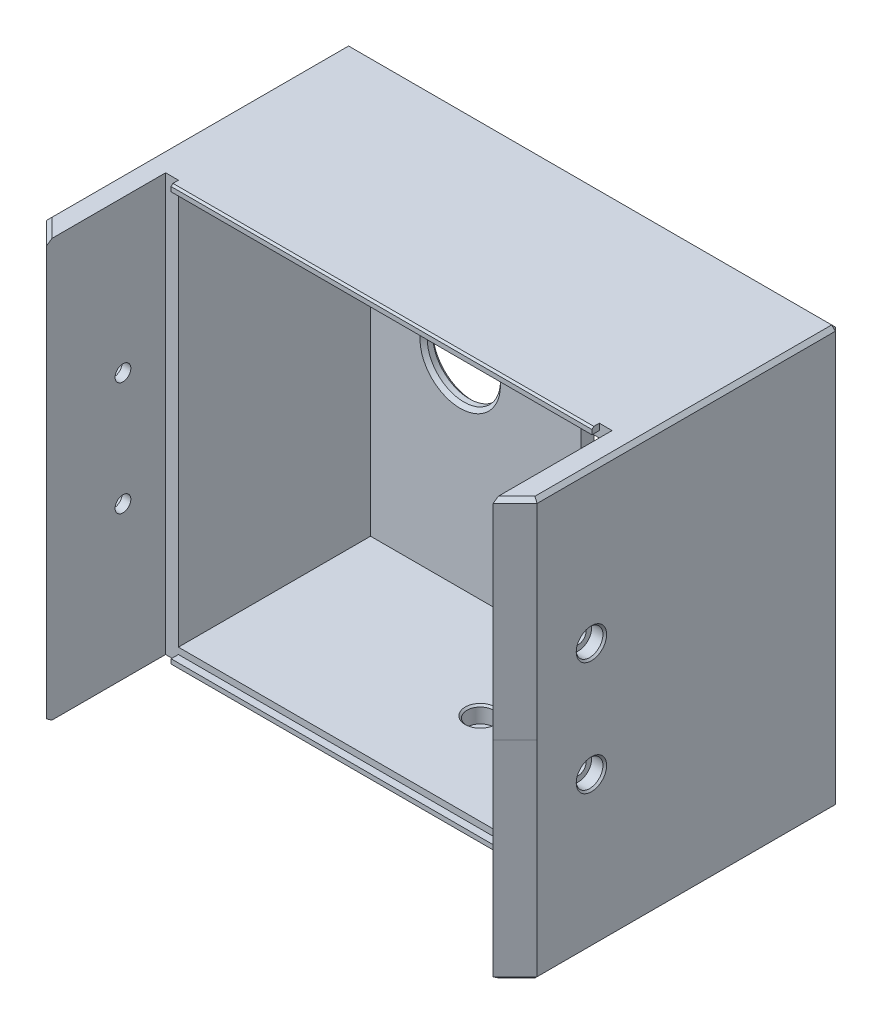
SolidWorks part; units mm, degrees
ref_plane "Front Plane" through (0, 0, 0) normal (0, 0, 1) x (1, 0, 0)
ref_plane "Top Plane" through (0, 0, 0) normal (0, 1, 0) x (1, 0, 0)
ref_plane "Right Plane" through (0, 0, 0) normal (1, 0, 0) x (0, 0, -1)
sketch "Sketch1" plane through (0, 0, 0) normal (0, 0, 1) x (1, 0, 0)
  line L1 (0, 0) -> (134, 0)
  line L2 (0, 0) -> (0, 57)
  line L3 (0, 57) -> (134, 57)
  line L4 (134, 0) -> (134, 57)
  dimension "D1" = 134
  dimension "D2" = 57
extrude "Boss-Extrude1" add sketch "Sketch1" along normal blind 250
sketch "Sketch2" plane through (0, 0, 250) normal (0, 0, 1) x (1, 0, 0)
  line L0 (0, 57) -> (0, 0) construction
  line L1 (9.5, 53.5) -> (124.5, 53.5)
  line L2 (9.5, 53.5) -> (9.5, 0)
  line L3 (9.5, 0) -> (124.5, 0)
  line L4 (124.5, 53.5) -> (124.5, 0)
  line L5 (134, 57) -> (0, 57) construction
  line L6 (134, 0) -> (134, 57) construction
  line L8 (0, 0) -> (134, 0) construction
  dimension "D1" = 9.5
  dimension "D2" = 3.5
  dimension "D3" = 9.5
extrude "Cut-Extrude1" cut sketch "Sketch2" against normal blind 246.5
sketch "Sketch3" plane through (0, 57, 0) normal (0, 1, 0) x (1, 0, 0)
  line L0 (134, -250) -> (0, -250) construction
  line L1 (9.5, -250) -> (124.5, -250)
  line L2 (9.5, -250) -> (9.5, -56)
  line L3 (9.5, -56) -> (124.5, -56)
  line L4 (124.5, -250) -> (124.5, -56)
  line L5 (0, -250) -> (0, 0) construction
  line L6 (134, -250) -> (134, 0) construction
  dimension "D1" = 9.5
  dimension "D2" = 9.5
  dimension "D3" = 194
extrude "Cut-Extrude2" cut sketch "Sketch3" against normal up to surface (3.5 mm away) up to face at (67, 53.5, 126.75)
sketch "Sketch4" plane through (0, 0, 0) normal (0, -1, 0) x (1, 0, 0)
  line L0 (67, 250) -> (67, 0) construction
  line L1 (0, 250) -> (9.5, 250) construction
  line L2 (9.5, 0) -> (124.5, 0) construction
  line L3 (0, 250) -> (0, 0) construction
  line L4 (0, 202.5) -> (6, 202.5)
  line L5 (0, 202.5) -> (0, 82.5)
  line L6 (0, 82.5) -> (6, 82.5)
  line L7 (6, 202.5) -> (6, 82.5)
  line L8 (128, 202.5) -> (128, 82.5)
  line L9 (134, 82.5) -> (128, 82.5)
  line L10 (134, 202.5) -> (134, 82.5)
  line L11 (134, 202.5) -> (128, 202.5)
  line L13 (0, 250) -> (9.5, 250) construction
  dimension "D1" = 47.5
  dimension "D2" = 6
  dimension "D3" = 120
extrude "Cut-Extrude3" cut sketch "Sketch4" against normal through all
chamfer "Chamfer1" distance 6 angle 45 4 edges at (6, 28.5, 202.5) (6, 28.5, 82.5) (128, 28.5, 82.5) (128, 28.5, 202.5)
sketch "Sketch5" plane through (134, 0, 0) normal (1, 0, 0) x (0, 0, -1)
  line L0 (-250, 15.5) -> (0, 15.5) construction
  line L4 (-250, 0) -> (-250, 57) construction
  line L5 (0, 0) -> (0, 57) construction
  line L6 (-250, 57) -> (-202.5, 57) construction
  circle A0 centre (-217.65, 15.5) radius 2.15
  circle A1 centre (-67.65, 15.5) radius 2.15
  dimension "D2" = 4.3
  dimension "D4" = 150
  dimension "D1" = 41.5
  dimension "D3" = 32.35
extrude "Cut-Extrude4" cut sketch "Sketch5" against normal blind 134
sketch "Sketch6" plane through (9.5, 0, 0) normal (1, 0, 0) x (0, 0, -1)
  line L0 (-56, 57) -> (-250, 57) construction
  line L1 (-250, 0) -> (-225, 0)
  line L2 (-250, 0) -> (-250, 4.5)
  line L3 (-250, 4.5) -> (-225, 4.5)
  line L4 (-225, 0) -> (-225, 4.5)
  dimension "D1" = 52.5
  dimension "D2" = 25
extrude "Boss-Extrude2" add sketch "Sketch6" along normal blind 115
sketch "Sketch7" plane through (134, 0, 0) normal (1, 0, 0) x (0, 0, -1)
  circle A0 centre (-217.65, 15.5) radius 3.65
  circle A1 centre (-67.65, 15.5) radius 3.65
  dimension "D1" = 7.3
extrude "Cut-Extrude5" cut sketch "Sketch7" against normal blind 3.6
sketch "Sketch8" plane through (0, 0, 0) normal (-1, 0, 0) x (0, 0, 1)
  circle A0 centre (217.65, 15.5) radius 3.65
  circle A1 centre (67.65, 15.5) radius 3.65
  dimension "D1" = 7.3
extrude "Cut-Extrude6" cut sketch "Sketch8" against normal blind 3.6
mirror "Mirror1" about plane through (0, 0, 0) normal (0, 1, 0) of "Cut-Extrude6", "Cut-Extrude5", "Boss-Extrude2", "Cut-Extrude4", "Chamfer1", "Cut-Extrude3", "Cut-Extrude2", "Cut-Extrude1", "Boss-Extrude1"
sketch "Sketch9" plane through (0, 0, 250) normal (0, 0, 1) x (1, 0, 0)
  line L0 (0, 0) -> (134, 0) construction
  line L1 (0, 57) -> (0, -57) construction
  line L2 (134, -57) -> (134, 57) construction
  circle A0 centre (25, 0) radius 1.65
  circle A1 centre (109, 0) radius 1.65
  dimension "D1" = 3.3
  dimension "D2" = 25
  dimension "D3" = 25
extrude "Cut-Extrude7" cut sketch "Sketch9" against normal blind 25
chamfer "Chamfer2" distance 1 angle 45 20 edges at (0, -57, 226.25) (3, -57, 199.5) (6, -57, 142.5) (3, -57, 85.5) (0, 57, 41.25) (3, 57, 199.5) (6, 57, 142.5) (3, 57, 85.5) (134, 57, 41.25) (131, 57, 199.5) (128, 57, 142.5) (131, 57, 85.5) (134, -57, 226.25) (131, -57, 199.5) (128, -57, 142.5) (131, -57, 85.5) (67, -57, 0) (134, 0, 0) (67, 57, 0) (0, 0, 0)
chamfer "Chamfer3" distance 0.5 angle 45 8 edges at (134, 15.5, 214) (134, 15.5, 64) (0, 15.5, 221.3) (0, 15.5, 71.3) (134, -15.5, 214) (134, -15.5, 64) (0, -15.5, 221.3) (0, -15.5, 71.3)
sketch "Sketch11" plane through (0, 0, 0) normal (0, 0, -1) x (-1, 0, 0)
  line L0 (-134, 0) -> (0, 0) construction
  line L1 (-134, -56) -> (-134, 56) construction
  line L2 (-67, 0) -> (-67, 14.25)
  line L3 (-67, 14.25) -> (-109.5, 14.25)
  line L4 (-115.5, 8.25) -> (-115.5, -8.25)
  line L5 (-109.5, -14.25) -> (-67, -14.25)
  line L6 (-67, -14.25) -> (-67, 0)
  line L7 (-109.5, 14.25) -> (-115.5, 8.25)
  line L8 (-115.5, -8.25) -> (-109.5, -14.25)
  circle A0 centre (-91.25, -20) radius 1.65
  circle A1 centre (-91.25, 20) radius 1.65
  point P7 (-115.5, -14.25)
  point P8 (-115.5, 14.25)
  dimension "D4" = 3.3
  dimension "D1" = 28.5
  dimension "D2" = 48.5
  dimension "D3" = 18.5
  dimension "D5" = 24.25
  dimension "D8" = 5.75
extrude "Cut-Extrude9" cut sketch "Sketch11" against normal up to surface (3.5 mm away) up to face at (67, 0, 3.5)
sketch "Sketch12" plane through (0, 57, 0) normal (0, 1, 0) x (1, 0, 0)
  line L0 (124.5, -56) -> (9.5, -56) construction
  line L1 (6, -56) -> (128, -56)
  line L2 (6, -56) -> (6, -196.5)
  line L4 (128, -56) -> (128, -196.5)
  line L5 (6, -196.5) -> (6, -88.5) construction
  line L6 (128, -88.5) -> (128, -196.5) construction
  line L9 (6, -196.5) -> (0, -196.5)
  line L10 (0, -196.5) -> (0, -250)
  line L11 (0, -250) -> (134, -250)
  line L12 (134, -250) -> (134, -196.5)
  line L13 (134, -196.5) -> (128, -196.5)
  line L14 (134, -202.5) -> (134, -250) construction
  line L15 (0, -250) -> (0, -202.5) construction
  line L16 (124.5, -250) -> (9.5, -250) construction
extrude "Cut-Extrude10" cut sketch "Sketch12" against normal through all
sketch "Sketch14" plane through (0, -57, 0) normal (0, -1, 0) x (1, 0, 0)
  line L0 (67, 56) -> (67, 0) construction
  line L1 (128, 56) -> (6, 56) construction
  line L2 (133, 0) -> (1, 0) construction
  line L3 (67, 41) -> (57, 41)
  line L4 (57, 41) -> (57, 21)
  line L5 (57, 21) -> (77, 21)
  line L6 (77, 21) -> (77, 41)
  line L7 (77, 41) -> (67, 41)
  dimension "D1" = 20
  dimension "D2" = 15
extrude "Boss-Extrude4" add sketch "Sketch14" along normal blind 10
chamfer "Chamfer4" distance 10 angle 45 2 edges at (77, -57, 31) (57, -57, 31)
sketch "Sketch18" plane through (0, 0, 41) normal (0, 0, 1) x (1, 0, 0)
  line L0 (1, -57) -> (133, -57)
  line L1 (133, -57) -> (129.5, -60.5)
  line L2 (129.5, -60.5) -> (4.5, -60.5)
  line L3 (4.5, -60.5) -> (1, -57)
  line L4 (0, -56) -> (1, -57) construction
  line L5 (134, -56) -> (133, -57) construction
  dimension "D1" = 3.5
extrude "Boss-Extrude5" add sketch "Sketch18" against normal up to surface and the other way blind 3.5 up to face at (67, -62, 21)
sketch "Sketch17" plane through (0, 0, 0) normal (0, 0, -1) x (-1, 0, 0)
  line L0 (-67, 0) -> (-1, 0) construction
  line L1 (-67, -14.25) -> (-67, 14.25) construction
  line L2 (-1, -56) -> (-1, 56) construction
  circle A0 centre (-34, 0) radius 10
  dimension "D1" = 20
extrude "Cut-Extrude13" cut sketch "Sketch17" against normal up to surface (3.5 mm away)
sketch "Sketch15" plane through (0, -67, 0) normal (0, -1, 0) x (1, 0, 0)
  line L0 (67, 41) -> (67, 21) construction
  line L1 (77, 41) -> (57, 41) construction
  line L2 (1, 21) -> (133, 21) construction
  circle A0 centre (67, 31) radius 2.15
  dimension "D1" = 4.3
extrude "Cut-Extrude11" cut sketch "Sketch15" against normal up to surface (13.5 mm away) up to face at (67, -53.5, 29.75)
sketch "Sketch16" plane through (0, -53.5, 0) normal (0, 1, 0) x (1, 0, 0)
  circle A0 centre (67, -31) radius 3.65
  circle A1 centre (67, -31) radius 2.15 construction
  dimension "D1" = 7.3
extrude "Cut-Extrude12" cut sketch "Sketch16" against normal blind 4.5
chamfer "Chamfer6" distance 1 angle 45 2 edges at (24, 0, 0) (44, 0, 3.5)
chamfer "Chamfer5" distance 0.5 angle 45 1 edges at (67, -53.5, 34.65)
sketch "Sketch19" plane through (0, -60.5, 0) normal (0, -1, 0) x (1, 0, 0)
  line L0 (4.5, 44.5) -> (129.5, 44.5) construction
  line L1 (50.5, 41) -> (83.5, 41)
  line L2 (50.5, 41) -> (50.5, 44.5)
  line L3 (50.5, 44.5) -> (83.5, 44.5)
  line L4 (83.5, 41) -> (83.5, 44.5)
  line L5 (83.5, 41) -> (83.5, 21) construction
extrude "Cut-Extrude14" cut sketch "Sketch19" against normal up to surface (3.5 mm away) up to face at (67, -57, 67.4179)
chamfer "Chamfer8" distance 3.5 angle 45 4 edges at (106.5, -60.5, 44.5) (83.5, -58.75, 44.5) (27.5, -60.5, 44.5) (50.5, -58.75, 44.5)
sketch "Sketch20" plane through (0, 0, 56) normal (0, 0, 1) x (1, 0, 0)
  line L0 (128, -57) -> (128, 57) construction
  line L1 (6, 57) -> (128, 57)
  line L2 (6, 57) -> (6, 55.25)
  line L3 (6, 55.25) -> (128, 55.25)
  line L4 (128, 57) -> (128, 55.25)
  line L6 (6, -57) -> (128, -57)
  line L7 (6, -57) -> (6, -55.25)
  line L8 (6, -55.25) -> (128, -55.25)
  line L9 (128, -57) -> (128, -55.25)
  dimension "D1" = 1.75
extrude "Boss-Extrude6" add sketch "Sketch20" along normal blind 2
sketch "Sketch21" plane through (0, 57, 0) normal (0, 1, 0) x (1, 0, 0)
  line L1 (6, -58) -> (9.5, -58)
  line L2 (6, -58) -> (6, -56)
  line L3 (6, -56) -> (9.5, -56)
  line L4 (9.5, -58) -> (9.5, -56)
  line L5 (128, -58) -> (124.5, -58)
  line L6 (128, -58) -> (128, -56)
  line L7 (128, -56) -> (124.5, -56)
  line L8 (124.5, -58) -> (124.5, -56)
  dimension "D1" = 3.5
  dimension "D2" = 2
extrude "Cut-Extrude15" cut sketch "Sketch21" against normal up to surface (114 mm away) up to face at (67, -57, 11)
chamfer "Chamfer9" distance 0.5 angle 45 2 edges at (67, -57, 58) (67, 57, 58)
